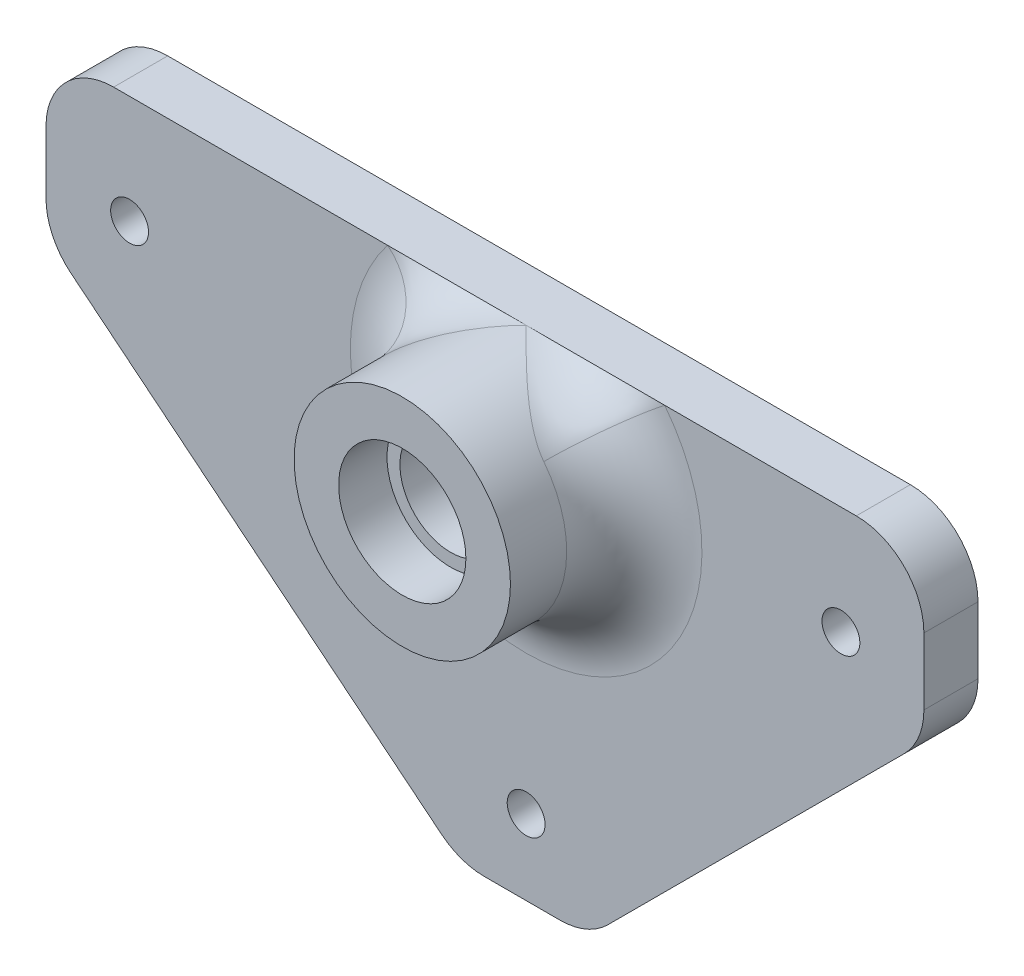
SolidWorks part; units mm, degrees
material "6061-T6 (SS)"
ref_plane "Front Plane" through (0, 0, 0) normal (0, 0, 1) x (1, 0, 0)
ref_plane "Top Plane" through (0, 0, 0) normal (0, 1, 0) x (1, 0, 0)
ref_plane "Right Plane" through (0, 0, 0) normal (1, 0, 0) x (0, 0, -1)
sketch "Sketch4" plane through (0, 0, 0) normal (0, 0, 1) x (1, 0, 0)
  line L0 (-18.4201, 29.1106) -> (-59.6414, 29.1106)
  line L4 (-18.4201, 21.4906) -> (-18.4201, 29.1106)
  line L5 (-34.1959, 5.7147) -> (-40.1926, 5.7147)
  line L7 (-59.6414, 21.4906) -> (-40.1926, 5.7147)
  line L8 (-34.1959, 5.7147) -> (-18.4201, 21.4906)
  line L10 (-59.6414, 29.1106) -> (-59.6414, 21.4906)
  point P0 (0, 0)
extrude "Extrude2" add sketch "Sketch4" along normal blind 2.54
sketch "Sketch8" plane through (0, 0, 2.54) normal (0, 0, 1) x (1, 0, 0)
  line L0 (-37.0966, 24.0306) -> (-22.3163, 24.0306) construction
  line L1 (-37.0966, 24.0306) -> (-37.0966, 9.2503) construction
  line L2 (-37.0966, 24.0306) -> (-55.7173, 24.0306) construction
  line L3 (-40.9066, 18.9506) -> (-33.2866, 18.9506) construction
  line L4 (-37.0966, 18.9506) -> (-37.0966, 29.1106) construction
  line L5 (-18.4201, 29.1106) -> (-59.6414, 29.1106) construction
  line L6 (-37.0966, 29.1106) -> (-37.0966, 24.0306) construction
sketch "Sketch5" plane through (0, 0, 2.54) normal (0, 0, 1) x (1, 0, 0)
  line L0 (-33.2866, 18.9506) -> (-40.9066, 18.9506) construction
  line L1 (-37.0966, 18.9506) -> (-37.0966, 29.1106) construction
  line L3 (-18.4201, 29.1106) -> (-59.6414, 29.1106) construction
  circle A0 centre (-37.0966, 24.0306) radius 5.08
extrude "Extrude3" add sketch "Sketch5" along normal blind 5.8166 and the other way blind 2.54
sketch "Sketch11" plane through (0, 0, 8.3566) normal (0, 0, 1) x (1, 0, 0)
  circle A0 centre (-37.0966, 24.0306) radius 2.3812
extrude "Extrude11" cut sketch "Sketch11" against normal through all
sketch "Sketch12" plane through (0, 0, 8.3566) normal (0, 0, 1) x (1, 0, 0)
  circle A0 centre (-37.0966, 24.0306) radius 2.9873
extrude "Extrude12" cut sketch "Sketch12" against normal blind 2.2708
sketch "Sketch14" plane through (0, 0, 0) normal (0, 0, -1) x (-1, 0, 0)
  circle A0 centre (37.0966, 24.0306) radius 2.9873
extrude "Extrude13" cut sketch "Sketch14" against normal blind 2.2708
hole_wizard "#50 (0.07) Diameter Hole1" positions "3DSketch1" profile "Sketch9" hole size "#50" standard "Ansi Inch"
sketch3d "3DSketch1"
  point P0 (-37.0966, 9.2503, 2.54)
  point P3 (-22.3163, 24.0306, 2.54)
sketch "Sketch9" plane through (-37.0966, 9.2503, 2.54) normal (1, 0, 0) x (0, -1, 0)
  line L0 (0, 0) -> (0, 5.6142)
  line L1 (0, 5.6142) -> (0.889, 5.08)
  line L2 (0.889, 5.08) -> (0.889, 0)
  line L5 (0.889, 0) -> (0, 0)
  line L10 (0, 5.6142) -> (-0.889, 5.08) construction
  line L11 (0, -6.35) -> (0, 107.95) construction
  dimension "Hole Dia." = 1.778
  dimension "Hole Depth" = 5.08
  dimension "Drill Angle" = 118
hole_wizard "#50 (0.07) Diameter Hole2" positions "3DSketch2" profile "Sketch10" hole size "#50" standard "Ansi Inch"
sketch3d "3DSketch2"
  point P0 (-55.7173, 24.0306, 2.54)
sketch "Sketch10" plane through (-55.7173, 24.0306, 2.54) normal (1, 0, 0) x (0, -1, 0)
  line L0 (0, 0) -> (0, 5.6142)
  line L1 (0, 5.6142) -> (0.889, 5.08)
  line L2 (0.889, 5.08) -> (0.889, 0)
  line L5 (0.889, 0) -> (0, 0)
  line L10 (0, 5.6142) -> (-0.889, 5.08) construction
  line L11 (0, -6.35) -> (0, 107.95) construction
  dimension "Hole Dia." = 1.778
  dimension "Hole Depth" = 5.08
  dimension "Drill Angle" = 118
fillet "Fillet1" radius 3.175 6 edges at (-59.6414, 21.4906, 1.27) (-40.1926, 5.7147, 1.27) (-34.1959, 5.7147, 1.27) (-18.4201, 21.4906, 1.27) (-18.4201, 29.1106, 1.27) (-59.6414, 29.1106, 1.27)
ref_plane "Plane1" through (0, 0, 12.065) normal (0, 0, -1) x (-1, 0, 0)
sketch "Sketch16" plane through (0, 0, 12.065) normal (0, 0, -1) x (-1, 0, 0)
  line L0 (37.0966, 24.0306) -> (37.0966, 29.1106) construction
  line L1 (37.0966, 29.1106) -> (61.2266, 29.1106) construction
fillet "Fillet2" radius 3.175 1 edges at (-32.0166, 24.0306, 2.54)
